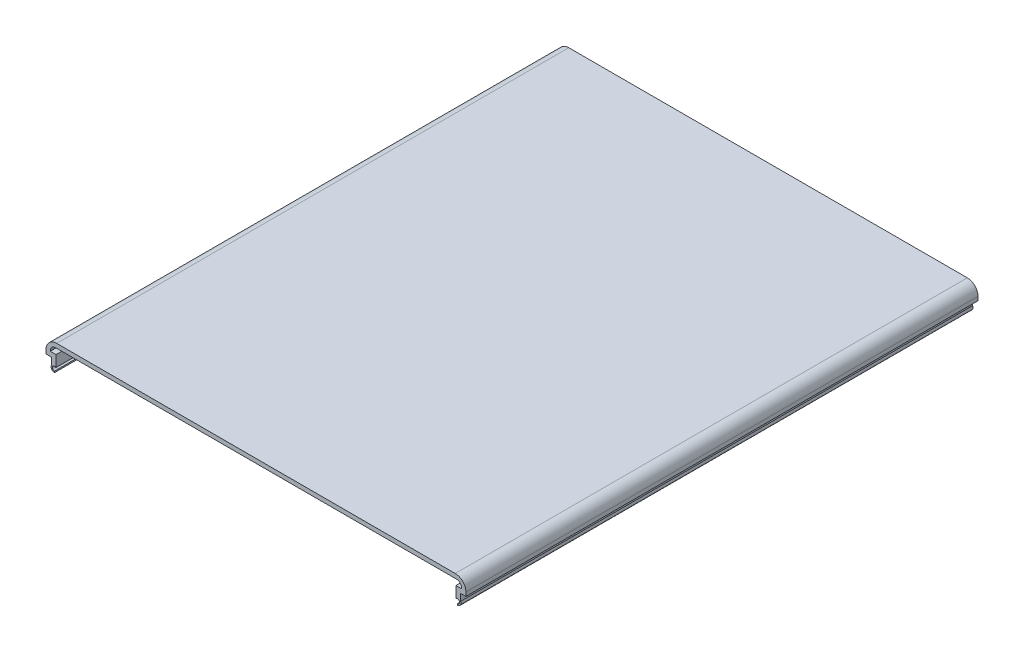
SolidWorks part; units mm, degrees
ref_plane "Front Plane" through (0, 0, 0) normal (0, 0, 1) x (1, 0, 0)
ref_plane "Top Plane" through (0, 0, 0) normal (0, 1, 0) x (1, 0, 0)
ref_plane "Right Plane" through (0, 0, 0) normal (1, 0, 0) x (0, 0, -1)
ref_plane "ExtTop" through (0, 0, 0) normal (0, 1, 0) x (1, 0, 0)
ref_plane "ExtRight" through (124.968, 0, 0) normal (1, 0, 0) x (0, 0, -1)
ref_plane "ExtLeft" through (-124.968, 0, 0) normal (1, 0, 0) x (0, 0, -1)
sketch "Sketch2" plane through (0, 0, 0) normal (0, 0, 1) x (1, 0, 0)
  line L0 (55, 0) -> (-55, 0) construction
  line L1 (-119.888, -15.7487) -> (-119.8812, -14.9232)
  line L2 (-119.253, -2.54) -> (119.253, -2.54)
  line L3 (-124.968, -55) -> (-124.968, 55) construction
  line L4 (-124.968, -6.35) -> (-124.968, -8.6655)
  line L5 (-124.968, -8.6655) -> (-121.793, -8.6655)
  line L6 (-121.793, -8.6655) -> (-121.793, -12.7803)
  line L7 (-119.1468, -12.622) -> (-118.9923, -12.622)
  line L8 (-118.9923, -6.0042) -> (-122.428, -6.0042)
  line L9 (-122.428, -6.0042) -> (-122.428, -5.715)
  line L10 (-118.618, 0) -> (118.618, 0)
  line L11 (0, 0) -> (0, -2.54) construction
  line L12 (118.9923, -12.622) -> (118.9923, -6.0042)
  line L13 (122.428, -6.0042) -> (122.428, -5.715)
  line L14 (118.9923, -6.0042) -> (122.428, -6.0042)
  line L15 (119.1468, -12.622) -> (118.9923, -12.622)
  line L16 (121.793, -8.6655) -> (121.793, -12.7803)
  line L17 (124.968, -8.6655) -> (121.793, -8.6655)
  line L18 (124.968, -6.35) -> (124.968, -8.6655)
  line L19 (-118.9923, -12.622) -> (-118.9923, -6.0042)
  line L20 (119.888, -15.7487) -> (119.8812, -14.9232)
  arc A0 (-124.968, -6.35) -> (-118.618, 0) centre (-118.618, -6.35) cw
  arc A1 (-122.428, -5.715) -> (-119.253, -2.54) centre (-119.253, -5.715) cw
  arc A2 (-121.793, -12.7803) -> (-119.888, -15.7487) centre (-119.888, -13.6532) ccw
  arc A3 (-119.8812, -14.9232) -> (-119.1468, -12.622) centre (-119.888, -13.6532) cw
  arc A4 (119.8812, -14.9232) -> (119.1468, -12.622) centre (119.888, -13.6532) ccw
  arc A5 (121.793, -12.7803) -> (119.888, -15.7487) centre (119.888, -13.6532) cw
  arc A6 (122.428, -5.715) -> (119.253, -2.54) centre (119.253, -5.715) ccw
  arc A7 (124.968, -6.35) -> (118.618, 0) centre (118.618, -6.35) ccw
  point P24 (-124.968, 0)
  point P28 (-119.253, -2.54)
  point P40 (124.968, 0)
  dimension "D5" = 239.776
  dimension "D1" = 6.35
  dimension "D6" = 3.175
  dimension "D2" = 2.0955
  dimension "D7" = 1.27
  dimension "D3" = 4.1148
  dimension "D4" = 3.175
  dimension "D9" = 2.54
  dimension "D10" = 0.471
  dimension "D11" = 5.08
extrude "MainBody" add sketch "Sketch2" along normal blind 304.8
ref_plane "BodyFront" through (0, 0, 304.8) normal (0, 0, 1) x (1, 0, 0)
ref_plane "BodyBack" through (0, 0, 0) normal (0, 0, -1) x (-1, 0, 0)
ref_plane "FBCenter" through (0, 0, 152.4) normal (0, 0, 1) x (1, 0, 0)
ref_plane "LRCenter" through (0, 0, 0) normal (1, 0, 0) x (0, 0, -1)
ref_axis "MntLeft" through (-119.888, -13.6532, 304.8) along (0, 0, -1)
ref_axis "MntRight" through (119.888, -13.6532, 304.8) along (0, 0, -1)
equation "\"ExtBodyDepth\"=12"
equation "\"D1@MainBody\" = \"ExtBodyDepth\""
